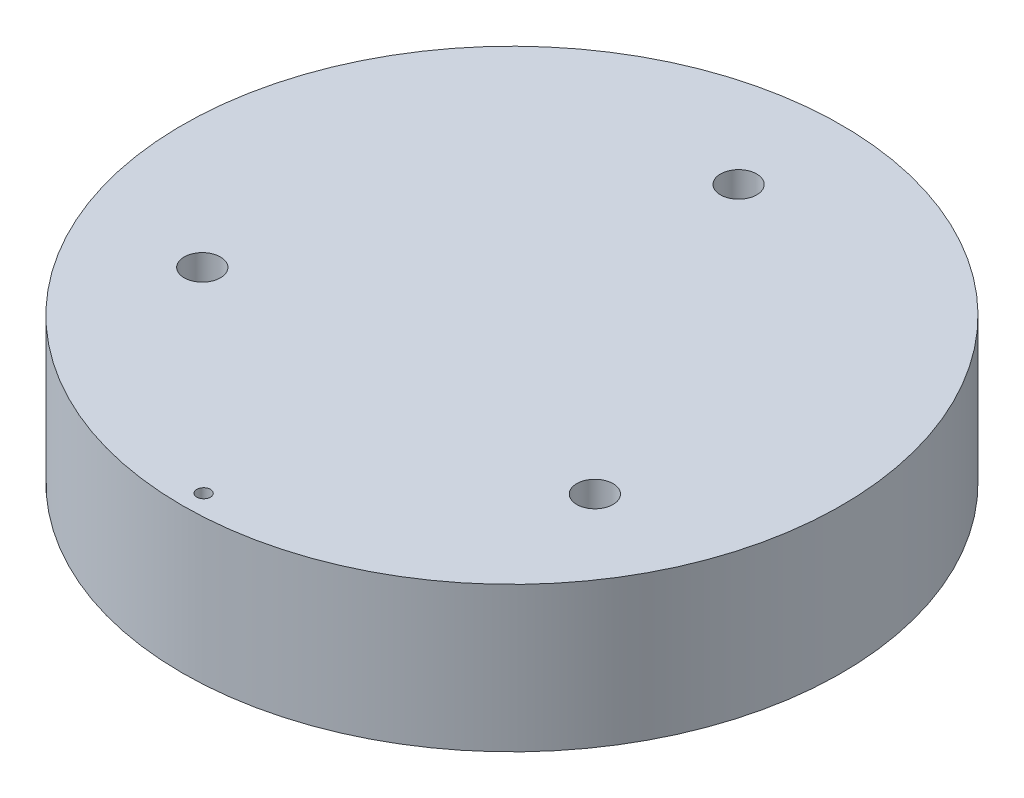
SolidWorks part; units mm, degrees
ref_plane "Ebene vorne" through (0, 0, 0) normal (0, 0, 1) x (1, 0, 0)
ref_plane "Ebene oben" through (0, 0, 0) normal (0, 1, 0) x (1, 0, 0)
ref_plane "Ebene rechts" through (0, 0, 0) normal (1, 0, 0) x (0, 0, -1)
sketch "Sketch1" plane through (0, 0, 0) normal (0, 1, 0) x (1, 0, 0)
  circle A0 centre (0, 0) radius 72.7
  dimension "D1" = 145.4
extrude "Boss-Extrude1" add sketch "Sketch1" along normal blind 32
sketch "Sketch2" plane through (0, 32, 0) normal (0, 1, 0) x (1, 0, 0)
  line L0 (0, 0) -> (0, 66.4755) construction
  circle A0 centre (0, 50) radius 4
  dimension "D1" = 8
  dimension "D2" = 50
extrude "Cut-Extrude1" cut sketch "Sketch2" against normal through all
ref_axis "Axis1" through (0, 33.6, 0) along (0, -1, 0)
pattern_circular "CirPattern1" count 3 over 360 about axis through (0, 33.6, 0) along (0, -1, 0) of "Cut-Extrude1"
sketch "Sketch3" plane through (0, 32, 0) normal (0, 1, 0) x (1, 0, 0)
  circle A0 centre (0, -68) radius 1.5
  point P2 (0, 0)
  dimension "D1" = 3
  dimension "D2" = 68
extrude "Cut-Extrude2" cut sketch "Sketch3" against normal through all
